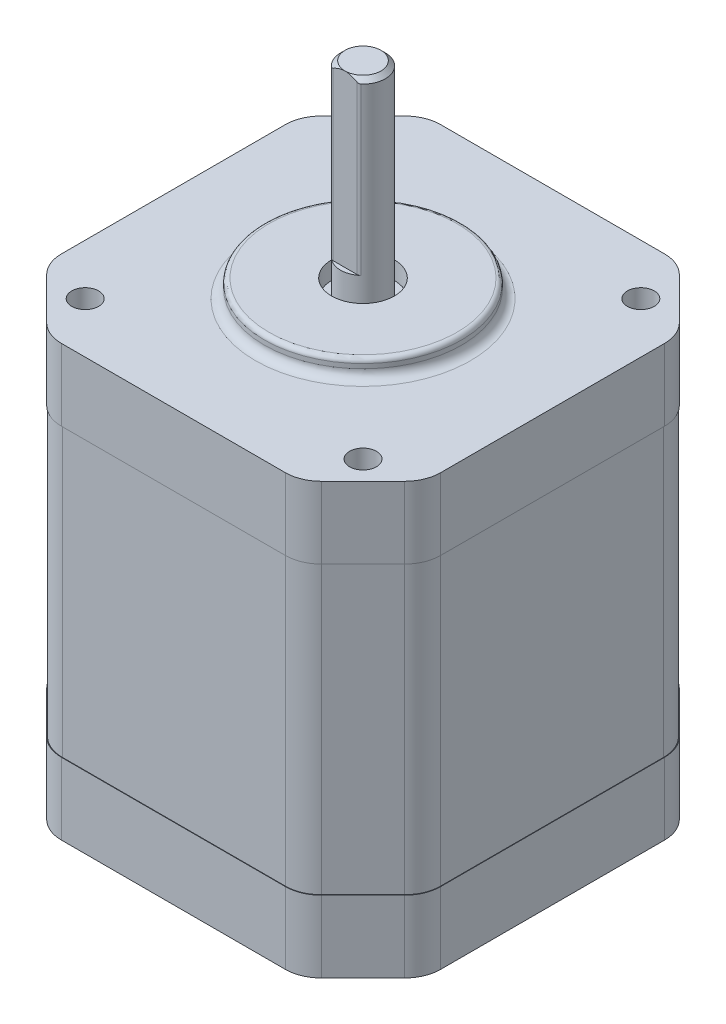
SolidWorks part; units mm, degrees
ref_plane "Plano frontal" through (0, 0, 0) normal (0, 0, 1) x (1, 0, 0)
ref_plane "Plano superior" through (0, 0, 0) normal (0, 1, 0) x (1, 0, 0)
ref_plane "Plano direito" through (0, 0, 0) normal (1, 0, 0) x (0, 0, -1)
sketch "Esboço1" plane through (0, 0, 0) normal (0, 1, 0) x (1, 0, 0)
  line L1 (-21.1, 21.1) -> (21.1, 21.1)
  line L2 (-21.1, 21.1) -> (-21.1, -21.1)
  line L3 (-21.1, -21.1) -> (21.1, -21.1)
  line L4 (21.1, 21.1) -> (21.1, -21.1)
  line L5 (-21.1, 21.1) -> (21.1, -21.1) construction
  line L6 (-21.1, -21.1) -> (21.1, 21.1) construction
  point P0 (0, 0)
  dimension "D1" = 42.2
  dimension "D2" = 42.2
extrude "Ressalto-extrusão1" add sketch "Esboço1" along normal mid plane 32
chamfer "Chanfro4" distance 7 angle 45 4 edges at (-21.1, 0, 21.1) (-21.1, 0, -21.1) (21.1, 0, -21.1) (21.1, 0, 21.1)
fillet "Filete3" radius 4 8 edges at (-14.1, 0, -21.1) (-21.1, 0, -14.1) (-14.1, 0, 21.1) (-21.1, 0, 14.1) (14.1, 0, -21.1) (21.1, 0, -14.1) (14.1, 0, 21.1) (21.1, 0, 14.1)
sketch "Esboço2" plane through (0, 16, 0) normal (0, 1, 0) x (1, 0, 0)
  line L1 (-21.15, 21.15) -> (21.15, 21.15)
  line L2 (-21.15, 21.15) -> (-21.15, -21.15)
  line L3 (-21.15, -21.15) -> (21.15, -21.15)
  line L4 (21.15, 21.15) -> (21.15, -21.15)
  line L5 (-21.15, 21.15) -> (21.15, -21.15) construction
  line L6 (-21.15, -21.15) -> (21.15, 21.15) construction
  point P0 (0, 0)
  dimension "D1" = 42.3
  dimension "D2" = 42.3
extrude "Ressalto-extrusão2" add sketch "Esboço2" along normal blind 8
chamfer "Chanfro5" distance 7 angle 45 4 edges at (21.15, 20, -21.15) (21.15, 20, 21.15) (-21.15, 20, 21.15) (-21.15, 20, -21.15)
fillet "Filete4" radius 4 8 edges at (-14.15, 20, -21.15) (-21.15, 20, -14.15) (-21.15, 20, 14.15) (-14.15, 20, 21.15) (14.15, 20, 21.15) (21.15, 20, 14.15) (21.15, 20, -14.15) (14.15, 20, -21.15)
mirror "Espelhar1" about plane through (0, 0, 0) normal (0, 1, 0) of "Filete4", "Ressalto-extrusão2", "Chanfro5"
sketch "Esboço3" plane through (0, 24, 0) normal (0, 1, 0) x (1, 0, 0)
  circle A0 centre (0, 0) radius 11
  circle A1 centre (0, 0) radius 3.5
  dimension "D1" = 22
  dimension "D2" = 7
extrude "Ressalto-extrusão3" add sketch "Esboço3" along normal blind 2
fillet "Filete5" radius 0.5 1 edges at (0, 26, 11)
fillet "Filete6" radius 1 1 edges at (0, 24, 11)
sketch "Esboço4" plane through (0, 24, 0) normal (0, 1, 0) x (1, 0, 0)
  circle A0 centre (-15.5, 15.5) radius 1.5
  circle A1 centre (0, 0) radius 3.5 construction
  dimension "D1" = 3
  dimension "D2" = 15.5
  dimension "D3" = 15.5
extrude "Corte-extrusão1" cut sketch "Esboço4" against normal blind 10
pattern_circular "PadrãoCircular1" count 4 over 360 about axis through (0, 26, 0) along (0, 1, 0) of "Corte-extrusão1"
sketch "Esboço5" plane through (0, 24, 0) normal (0, 1, 0) x (1, 0, 0)
  circle A0 centre (0, 0) radius 2.5
  dimension "D1" = 5
extrude "Ressalto-extrusão4" add sketch "Esboço5" along normal blind 4
sketch "Esboço6" plane through (0, 28, 0) normal (0, 1, 0) x (1, 0, 0)
  line L0 (-1.5, -2) -> (1.5, -2)
  circle A0 centre (0, 0) radius 2.5 construction
  circle A1 centre (0, 0) radius 2.5
  circle M2 centre (0, 0) radius 2.5
  dimension "D1" = 2
extrude "Ressalto-extrusão5" add sketch "Esboço6" along normal blind 19 contours L0 M2 region at (0, 28, -0.1209)
chamfer "Chanfro3" distance 0.5 angle 45 1 edges at (0, 47, -2.5)
fillet "Filete2" radius 0.5 2 edges
